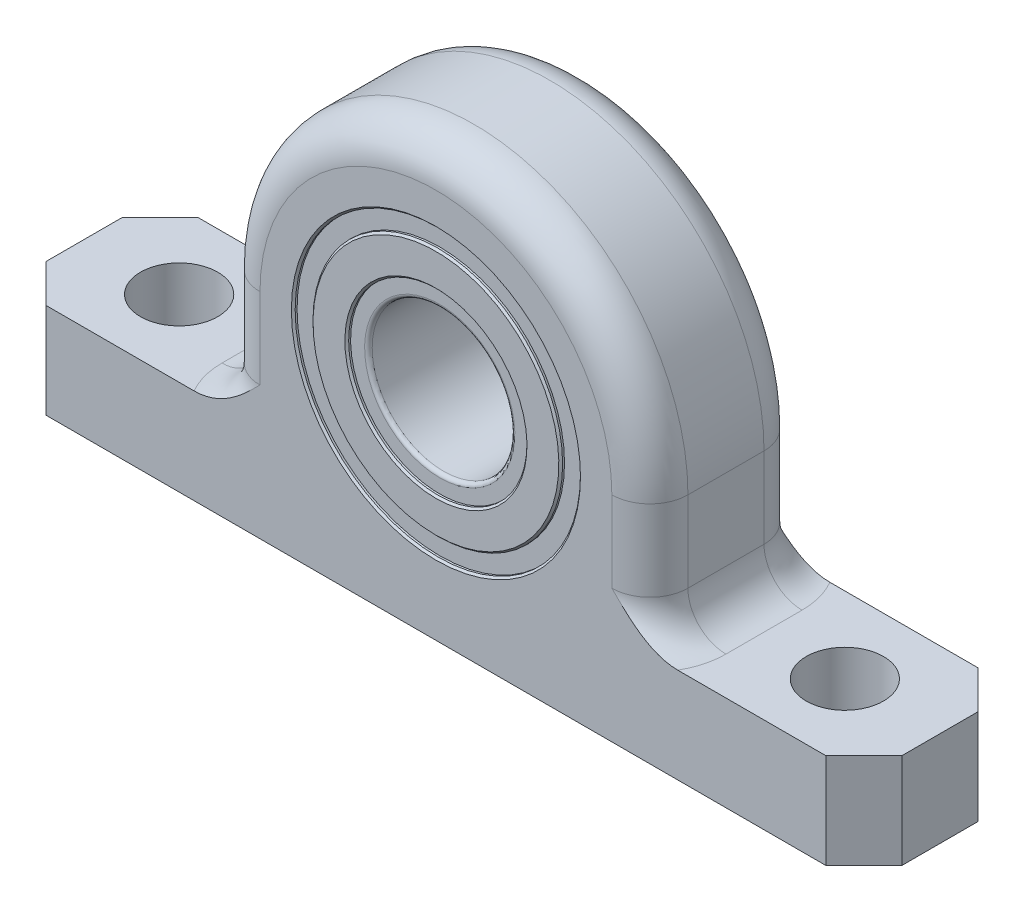
SolidWorks part; units mm, degrees
ref_plane "Front Plane" through (0, 0, 0) normal (0, 0, 1) x (1, 0, 0)
ref_plane "Top Plane" through (0, 0, 0) normal (0, 1, 0) x (1, 0, 0)
ref_plane "Right Plane" through (0, 0, 0) normal (1, 0, 0) x (0, 0, -1)
sketch "Sketch1" plane through (0, 0, 0) normal (0, 0, 1) x (1, 0, 0)
  line L0 (14.2875, 0) -> (14.2875, -7.9375)
  line L1 (14.2875, -7.9375) -> (28.575, -7.9375)
  line L2 (28.575, -7.9375) -> (28.575, -14.2875)
  line L3 (28.575, -14.2875) -> (-28.575, -14.2875)
  line L4 (-28.575, -14.2875) -> (-28.575, -7.9375)
  line L5 (-28.575, -7.9375) -> (-14.2875, -7.9375)
  line L6 (-14.2875, -7.9375) -> (-14.2875, 0)
  circle A0 centre (0, 0) radius 4.7625
  arc A1 (14.2875, 0) -> (-14.2875, 0) centre (0, 0) ccw
  circle A2 centre (0, 0) radius 9.525
  dimension "D1" = 19.05
sketch "Sketch2" plane through (0, 0, 0) normal (0, 1, 0) x (1, 0, 0)
  line L0 (0, 5.08) -> (0, -5.08) construction
  line L1 (-22.225, 0) -> (22.225, 0) construction
  circle A0 centre (22.225, 0) radius 2.5797
  circle A1 centre (-22.225, 0) radius 2.5797
sketch "Sketch3" plane through (0, 0, 0) normal (0, 0, 1) x (1, 0, 0)
  line L0 (14.2875, 0) -> (14.2875, -7.9375) construction
  line L1 (28.575, -7.9375) -> (28.575, -14.2875) construction
  line L2 (14.2875, -7.9375) -> (28.575, -7.9375) construction
  line L3 (28.575, -14.2875) -> (-28.575, -14.2875) construction
  line L4 (-28.575, -14.2875) -> (-28.575, -7.9375) construction
  line L5 (-28.575, -7.9375) -> (-14.2875, -7.9375) construction
  line L6 (-14.2875, -7.9375) -> (-14.2875, 0) construction
  line L7 (14.2875, 0) -> (14.2875, -7.9375)
  line L8 (28.575, -7.9375) -> (28.575, -14.2875)
  line L9 (14.2875, -7.9375) -> (28.575, -7.9375)
  line L10 (28.575, -14.2875) -> (-28.575, -14.2875)
  line L11 (-28.575, -14.2875) -> (-28.575, -7.9375)
  line L12 (-28.575, -7.9375) -> (-14.2875, -7.9375)
  line L13 (-14.2875, -7.9375) -> (-14.2875, 0)
  arc A0 (14.2875, 0) -> (-14.2875, 0) centre (0, 0) ccw construction
  circle A1 centre (0, 0) radius 9.525 construction
  arc A2 (14.2875, 0) -> (-14.2875, 0) centre (0, 0) ccw
  circle A3 centre (0, 0) radius 9.525
extrude "Extrude1" add sketch "Sketch3" along normal up to vertex (5.08 mm away) and the other way up to vertex (5.08 mm away) up to point (0, 0, 5.08) other way up to point (0, 0, -5.08)
sketch "Sketch4" plane through (0, -7.9375, 0) normal (0, 1, 0) x (1, 0, 0)
  line L0 (-28.575, 5.08) -> (-28.575, 2.54)
  line L1 (-28.575, -5.08) -> (-28.575, 5.08) construction
  line L2 (-28.575, 2.54) -> (-26.035, 5.08)
  line L3 (-14.2875, 5.08) -> (-28.575, 5.08) construction
  line L4 (-26.035, 5.08) -> (-28.575, 5.08)
  line L5 (0, 0) -> (0, 5.08) construction
  line L6 (0, 0) -> (-22.225, 0) construction
  line L7 (26.035, 5.08) -> (28.575, 5.08)
  line L8 (28.575, 2.54) -> (26.035, 5.08)
  line L9 (28.575, 5.08) -> (28.575, 2.54)
  line L10 (28.575, -5.08) -> (28.575, -2.54)
  line L11 (28.575, -2.54) -> (26.035, -5.08)
  line L12 (26.035, -5.08) -> (28.575, -5.08)
  line L13 (-26.035, -5.08) -> (-28.575, -5.08)
  line L14 (-28.575, -2.54) -> (-26.035, -5.08)
  line L15 (-28.575, -5.08) -> (-28.575, -2.54)
  circle A0 centre (-22.225, 0) radius 2.5797 construction
  circle A1 centre (22.225, 0) radius 2.5797 construction
  circle A2 centre (-22.225, 0) radius 2.5797
  circle A3 centre (22.225, 0) radius 2.5797
  dimension "D1" = 45
  dimension "D2" = 2.54
extrude "Cut-Extrude1" cut sketch "Sketch4" against normal through all
fillet "Fillet1" radius 2.54 6 edges at (14.2875, -3.9687, -5.08) (-14.2875, -3.9687, -5.08) (14.2875, -3.9687, 5.08) (-14.2875, -3.9687, 5.08) (0, 14.2875, -5.08) (0, 14.2875, 5.08)
fillet "Fillet2" radius 2.54 6 edges at (-13.5436, -7.9375, 4.3361) (-13.5436, -7.9375, -4.3361) (13.5436, -7.9375, 4.3361) (13.5436, -7.9375, -4.3361) (-14.2875, -7.9375, 0) (14.2875, -7.9375, 0)
chamfer "Chamfer1" distance 0.127 angle 45 2 edges at (9.525, 0, -5.08) (9.525, 0, 5.08)
sketch "Sketch5" plane through (0, 0, 0) normal (1, 0, 0) x (0, 0, -1)
  line L0 (0, 0) -> (0, 9.525) construction
  line L1 (0, 9.525) -> (0, -9.525) construction
  line L2 (0, 4.7625) -> (0, -4.7625) construction
  line L3 (-4.826, 9.525) -> (-4.826, 8.3344)
  line L4 (-4.826, 8.3344) -> (-5.08, 8.3344)
  line L5 (-5.08, 8.3344) -> (-5.08, 5.9531)
  line L6 (-5.08, 5.9531) -> (-4.826, 5.9531)
  line L7 (-4.826, 5.9531) -> (-4.826, 4.7625)
  line L8 (-4.826, 4.7625) -> (4.826, 4.7625)
  line L9 (0, 4.7625) -> (0, 9.525) construction
  line L10 (-4.826, 9.525) -> (4.826, 9.525)
  line L11 (-5.08, 11.7475) -> (-5.08, 0) construction
  line L12 (4.826, 5.9531) -> (4.826, 4.7625)
  line L13 (5.08, 5.9531) -> (4.826, 5.9531)
  line L14 (5.08, 8.3344) -> (5.08, 5.9531)
  line L15 (4.826, 8.3344) -> (5.08, 8.3344)
  line L16 (4.826, 9.525) -> (4.826, 8.3344)
  line L17 (0, 0) -> (-5.08, 0) construction
  point P6 (0, 4.7625)
  dimension "D2" = 4.7625
  dimension "D3" = 2.3813
revolve "Revolve1" add sketch "Sketch5" angle 360 about L17
fillet "Fillet3" radius 0.254 2 edges at (0, 4.7625, 4.826) (0, 4.7625, -4.826)
chamfer "Chamfer2" distance 0.127 angle 45 4 edges at (0, 5.9531, -5.08) (0, 8.3344, -5.08) (0, 8.3344, 5.08) (0, 5.9531, 5.08)
equation "\"D1@Sketch1\" = \"shaft dia@Sketch1\"*2."
equation "\"D2@Sketch4\" = \"E@Sketch2\"/4"
equation "\"D1@Fillet1\" = \"D2@Sketch4\""
equation "\"D1@Fillet2\" = \"D1@Fillet1\""
equation "\"D3@Sketch5\" = \"D2@Sketch5\"/2"
